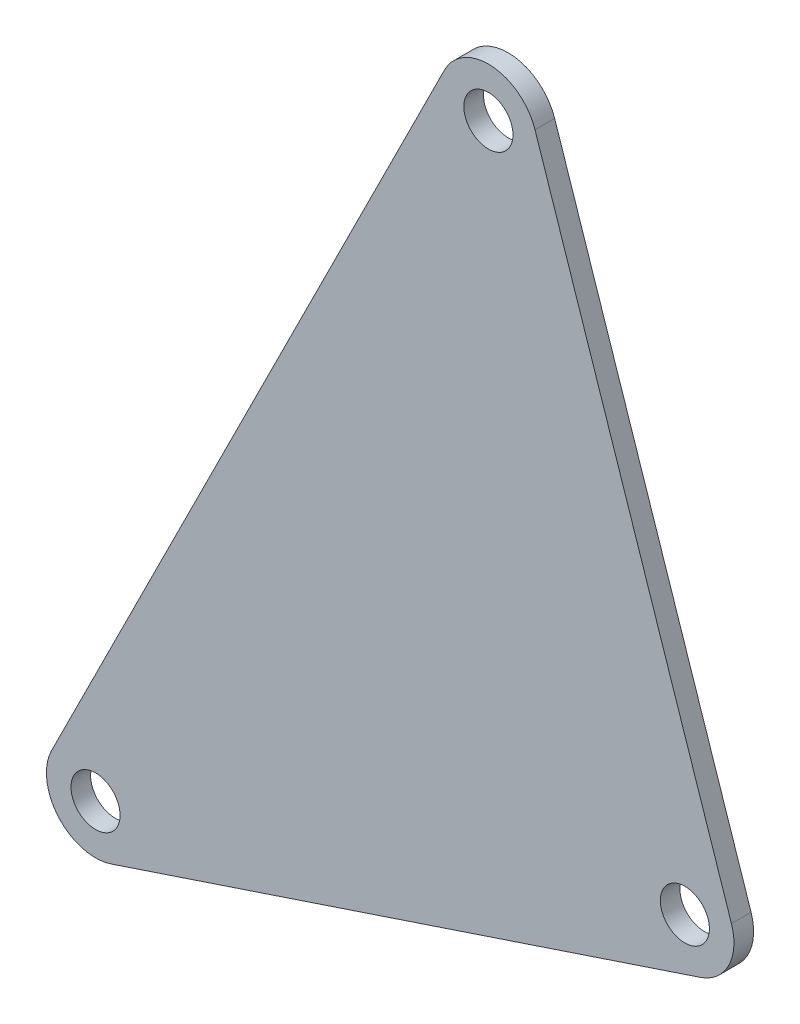
SolidWorks part; units mm, degrees
ref_plane "Front Plane" through (0, 0, 0) normal (0, 0, 1) x (1, 0, 0)
ref_plane "Top Plane" through (0, 0, 0) normal (0, 1, 0) x (1, 0, 0)
ref_plane "Right Plane" through (0, 0, 0) normal (1, 0, 0) x (0, 0, -1)
sketch "Sketch1" plane through (0, 0, 0) normal (0, 0, 1) x (1, 0, 0)
  line L0 (-76.2, 0) -> (0, 0) construction
  line L1 (0, 0) -> (0, 25.4) construction
  line L2 (0, 25.4) -> (0, 101.6) construction
  line L3 (0, 101.6) -> (-25.4, 101.6) construction
  line L4 (-24.2237, 118.1516) -> (-88.7355, -10.872)
  line L5 (-76.2, 0) -> (-25.4, 101.6) construction
  line L6 (-25.4, 101.6) -> (0, 25.4) construction
  line L7 (0, 25.4) -> (-76.2, 0) construction
  line L8 (-88.7355, -10.872) -> (8.0322, 21.3839)
  line L9 (8.0322, 21.3839) -> (-24.2237, 118.1516)
  circle A0 centre (-76.2, 0) radius 3.175
  circle A1 centre (0, 25.4) radius 3.175
  circle A2 centre (-25.4, 101.6) radius 3.175
  point P13 (-202.5902, -23.4235)
  point P15 (8.0322, 46.7839)
  point P16 (-49.4505, 219.2319)
  point P17 (0, 0)
  point P18 (-164.7162, -10.7989)
  dimension "D5" = 6.35
  dimension "D6" = 6.35
  dimension "D7" = 6.35
  dimension "D1" = 76.2
  dimension "D2" = 25.4
  dimension "D3" = 76.2
  dimension "D4" = 25.4
  dimension "D8" = 6.35
  dimension "D9" = 6.35
  dimension "D10" = 6.35
extrude "Boss-Extrude1" add sketch "Sketch1" along normal blind 2.54
fillet "Fillet1" radius 6.35 3 edges at (-88.7355, -10.872, 1.27) (8.0322, 21.3839, 1.27) (-24.2237, 118.1516, 1.27)
